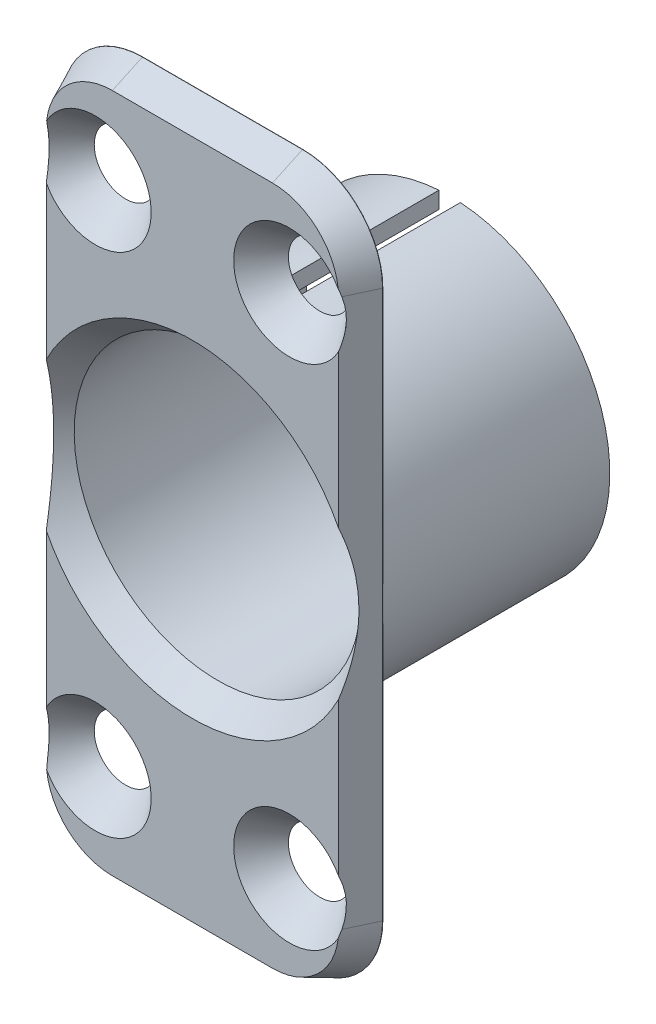
SolidWorks part; units mm, degrees
ref_plane "Front Plane" through (0, 0, 0) normal (0, 0, 1) x (1, 0, 0)
ref_plane "Top Plane" through (0, 0, 0) normal (0, 1, 0) x (1, 0, 0)
ref_plane "Right Plane" through (0, 0, 0) normal (1, 0, 0) x (0, 0, -1)
sketch "Sketch1" plane through (0, 0, 0) normal (0, 0, 1) x (1, 0, 0)
  line L1 (6.35, 28.075) -> (-6.35, 28.075)
  line L2 (12.7, 21.725) -> (12.7, -21.725)
  line L3 (6.35, -28.075) -> (-6.35, -28.075)
  line L4 (-12.7, 21.725) -> (-12.7, -21.725)
  line L5 (12.7, 28.075) -> (-12.7, -28.075) construction
  line L6 (12.7, -28.075) -> (-12.7, 28.075) construction
  arc A0 (6.35, 28.075) -> (12.7, 21.725) centre (6.35, 21.725) cw
  arc A1 (6.35, -28.075) -> (12.7, -21.725) centre (6.35, -21.725) ccw
  arc A2 (-6.35, -28.075) -> (-12.7, -21.725) centre (-6.35, -21.725) cw
  arc A3 (-12.7, 21.725) -> (-6.35, 28.075) centre (-6.35, 21.725) cw
  point P0 (0, 0)
  dimension "D3" = 6.35
  dimension "D1" = 25.4
  dimension "D2" = 56.15
extrude "Boss-Extrude1" add sketch "Sketch1" along normal blind 2.4
sketch "Sketch2" plane through (0, 0, 0) normal (0, 0, -1) x (-1, 0, 0)
  line L1 (-6.35, 28.075) -> (6.35, 28.075) construction
  line L2 (-6.35, 28.075) -> (6.35, 28.075) construction
  line L3 (6.35, -28.075) -> (-6.35, -28.075) construction
  line L4 (12.7, 21.725) -> (12.7, -21.725) construction
  line L5 (-12.7, -21.725) -> (-12.7, 21.725) construction
  circle A0 centre (-7.7, 20.1248) radius 2
  circle A1 centre (-7.7, -20.125) radius 2
  circle A2 centre (7.7, 20.125) radius 2
  circle A3 centre (7.7, -20.125) radius 2
  dimension "D1" = 4
  dimension "D2" = 4
  dimension "D5" = 4
  dimension "D6" = 7.95
  dimension "D7" = 7.95
  dimension "D8" = 4
  dimension "D9" = 5
  dimension "D10" = 5
  dimension "D3" = 7.95
  dimension "D11" = 5
  dimension "D12" = 5
  dimension "D4" = 7.9502
extrude "Cut-Extrude1" cut sketch "Sketch2" against normal through all
chamfer "Chamfer1" distance 2.38 angle 25 8 edges at (-10.8401, 26.2151, 2.4) (0, 28.075, 2.4) (10.8401, 26.2151, 2.4) (12.7, 0, 2.4) (10.8401, -26.2151, 2.4) (0, -28.075, 2.4) (-10.8401, -26.2151, 2.4) (-12.7, 0, 2.4) first distance on face at (-10.1826, 25.5576, 1.2) first distance on face at (0, 28.075, 1.2) first distance on face at (10.1826, 25.5576, 1.2) first distance on face at (12.7, 0, 1.2) first distance on face at (10.1826, -25.5576, 1.2) first distance on face at (0, -28.075, 1.2) first distance on face at (-10.1826, -25.5576, 1.2) first distance on face at (-12.7, 0, 1.2)
sketch "Sketch3" plane through (0, 0, 0) normal (0, 0, -1) x (-1, 0, 0)
  circle A2 centre (0, 0) radius 12.7
  circle A3 centre (0, 0) radius 11.375
  dimension "D1" = 25.4
  dimension "D2" = 22.75
extrude "Boss-Extrude2" add sketch "Sketch3" along normal blind 18
sketch "Sketch4" plane through (0, 0, 0) normal (0, 0, -1) x (-1, 0, 0)
  circle A0 centre (0, 0) radius 11.375
  dimension "D1" = 22.75
extrude "Cut-Extrude2" cut sketch "Sketch4" against normal blind 30
chamfer "Chamfer2" distance 3 angle 39 4 edges at (5.7, -20.125, 2.4) (-9.7, -20.125, 2.4) (5.7, 20.1248, 2.4) (-9.7, 20.125, 2.4) first distance on face at (5.7, -20.125, 2.4) first distance on face at (-9.7, -20.125, 2.4) first distance on face at (5.7, 20.1248, 2.4) first distance on face at (-9.7, 20.125, 2.4)
chamfer "Chamfer3" distance 2 angle 39 1 edges at (-11.375, 0, 2.4) first distance on face at (-11.375, 0, -18)
sketch "Sketch5" plane through (0, 0, -18) normal (0, 0, -1) x (-1, 0, 0)
  line L2 (-0.85, 11.3432) -> (-0.85, 12.75)
  line L3 (-0.85, 12.75) -> (0.85, 12.75)
  line L4 (0.85, 11.3432) -> (0.85, 12.75)
  line L5 (0, 11.375) -> (0.85, 12.75) construction
  line L6 (-0.85, 12.75) -> (0, 11.375) construction
  arc A0 (0.85, 11.3432) -> (-0.85, 11.3432) centre (0, 0) ccw
  point P3 (0, 11.375)
  dimension "D1" = 1.7
extrude "Cut-Extrude3" cut sketch "Sketch5" against normal through all
equation "\"0..005in\"=0.393701"
